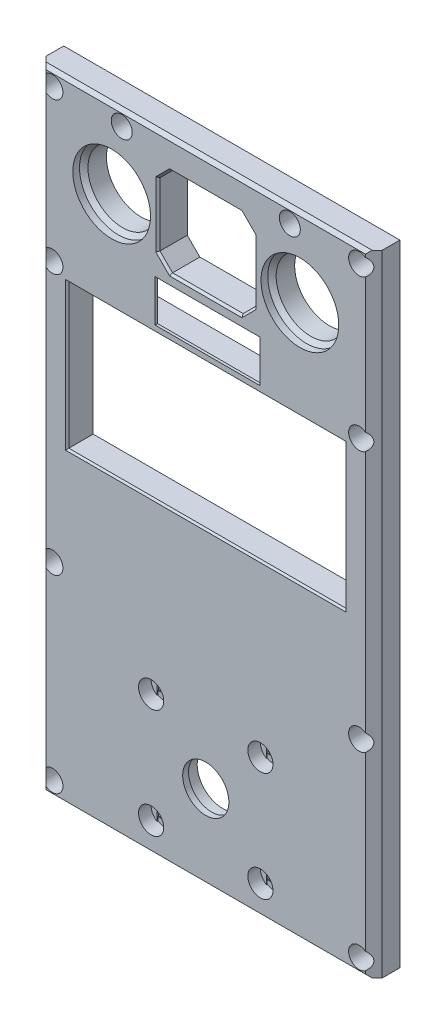
SolidWorks part; units mm, degrees
ref_plane "Front Plane" through (0, 0, 0) normal (0, 0, 1) x (1, 0, 0)
ref_plane "Top Plane" through (0, 0, 0) normal (0, 1, 0) x (1, 0, 0)
ref_plane "Right Plane" through (0, 0, 0) normal (1, 0, 0) x (0, 0, -1)
sketch "Sketch1" plane through (0, 0, 0) normal (0, 0, 1) x (1, 0, 0)
  line L1 (-40, -75) -> (40, -75)
  line L2 (-40, -75) -> (-40, 75)
  line L3 (-40, 75) -> (40, 75)
  line L4 (40, -75) -> (40, 75)
  line L5 (-40, -75) -> (40, 75) construction
  line L6 (-40, 75) -> (40, -75) construction
  line L7 (-33, -68) -> (33, -68)
  line L8 (-33, -68) -> (-33, 68)
  line L9 (-33, 68) -> (33, 68)
  line L10 (33, -68) -> (33, 68)
  line L11 (-33, -68) -> (33, 68) construction
  line L12 (-33, 68) -> (33, -68) construction
  point P0 (0, 0)
  point P6 (0, 0)
  dimension "D1" = 150
  dimension "D2" = 80
  dimension "D3" = 7
  dimension "D4" = 7
extrude "Boss-Extrude1" add sketch "Sketch1" along normal blind 7
sketch "Sketch2" plane through (0, 0, 7) normal (0, 0, 1) x (1, 0, 0)
  line L0 (33, -68) -> (33, 68) construction
  line L1 (-33, -68) -> (33, -68)
  line L2 (-33, -68) -> (-33, -32)
  line L3 (-33, -32) -> (33, -32)
  line L4 (33, -68) -> (33, -32)
  dimension "D1" = 36
extrude "Boss-Extrude2" add sketch "Sketch2" against normal up to surface (7 mm away) up to face at (0, 0, 0)
sketch "Sketch3" plane through (0, 0, 0) normal (0, 0, -1) x (-1, 0, 0)
  line L0 (0, -75) -> (0, -55) construction
  line L1 (40, -75) -> (-40, -75) construction
  circle A0 centre (0, -55) radius 5.5
  dimension "D1" = 11
  dimension "D2" = 20
extrude "Cut-Extrude1" cut sketch "Sketch3" against normal through all
sketch "Sketch4" plane through (0, 0, 0) normal (0, 0, -1) x (-1, 0, 0)
  circle A0 centre (0, -55) radius 6.05
  dimension "D1" = 12.1
extrude "Cut-Extrude2" cut sketch "Sketch4" against normal offset from surface (5.6 mm away) 1.4 up to face at (-5.5, -55, 7)
sketch "Sketch5" plane through (0, 0, 0) normal (0, 0, -1) x (-1, 0, 0)
  circle A0 centre (0, -55) radius 11.1
  dimension "D1" = 22.2
extrude "Cut-Extrude3" cut sketch "Sketch5" against normal offset from surface (3 mm away) 2.6 up to face at (-6.05, -55, 5.6)
sketch "Sketch6" plane through (0, 0, 0) normal (0, 0, -1) x (-1, 0, 0)
  line L1 (-13, -68) -> (13, -68) construction
  line L2 (-13, -68) -> (-13, -42) construction
  line L3 (-13, -42) -> (13, -42) construction
  line L4 (13, -68) -> (13, -42) construction
  line L5 (-13, -68) -> (13, -42) construction
  line L6 (-13, -42) -> (13, -68) construction
  circle A0 centre (-13, -42) radius 1.6
  circle A1 centre (13, -42) radius 1.6
  circle A2 centre (13, -68) radius 1.6
  circle A3 centre (-13, -68) radius 1.6
  point P0 (0, -55)
  dimension "D2" = 3.2
  dimension "D1" = 26
extrude "Cut-Extrude4" cut sketch "Sketch6" against normal through all
sketch "Sketch7" plane through (0, 0, 0) normal (0, 0, -1) x (-1, 0, 0)
  line L1 (-25, -74) -> (25, -74)
  line L2 (-25, -74) -> (-25, -36)
  line L3 (-25, -36) -> (25, -36)
  line L4 (25, -74) -> (25, -36)
  line L5 (-25, -74) -> (25, -36) construction
  line L6 (-25, -36) -> (25, -74) construction
  point P0 (0, -55)
  dimension "D1" = 50
  dimension "D2" = 38
extrude "Cut-Extrude5" cut sketch "Sketch7" against normal blind 1
sketch "Sketch8" plane through (0, 0, 7) normal (0, 0, 1) x (1, 0, 0)
  circle A0 centre (-13, -42) radius 3
  circle A1 centre (13, -42) radius 3
  circle A2 centre (13, -68) radius 3
  circle A3 centre (-13, -68) radius 3
  dimension "D1" = 6
extrude "Cut-Extrude6" cut sketch "Sketch8" against normal blind 3
sketch "Sketch9" plane through (0, 0, 7) normal (0, 0, 1) x (1, 0, 0)
  line L0 (-40, 75) -> (-40, -75) construction
  line L1 (-36.5, -71.5) -> (36.5, -71.5) construction
  line L2 (-36.5, -71.5) -> (-36.5, 71.5) construction
  line L3 (-36.5, 71.5) -> (36.5, 71.5) construction
  line L4 (36.5, -71.5) -> (36.5, 71.5) construction
  line L5 (-36.5, -71.5) -> (36.5, 71.5) construction
  line L6 (-36.5, 71.5) -> (36.5, -71.5) construction
  line L7 (40, 75) -> (-40, 75) construction
  circle A0 centre (-36.5, 71.5) radius 1.35
  circle A1 centre (36.5, 71.5) radius 1.35
  circle A2 centre (36.5, -71.5) radius 1.35
  circle A3 centre (-36.5, -71.5) radius 1.35
  circle A6 centre (-36.5, 35.5) radius 1.35
  circle A7 centre (-36.5, -26.5) radius 1.35
  circle A8 centre (36.5, -26.5) radius 1.35
  circle A9 centre (36.5, 35.5) radius 1.35
  point P0 (0, 0)
  dimension "D3" = 2.7
  dimension "D4" = 45
  dimension "D5" = 36
  dimension "D1" = 3.5
  dimension "D2" = 3.5
extrude "Cut-Extrude7" cut sketch "Sketch9" against normal through all
sketch "Sketch10" plane through (0, 0, 7) normal (0, 0, 1) x (1, 0, 0)
  circle A0 centre (-36.5, 71.5) radius 2.5
  circle A1 centre (36.5, 71.5) radius 2.5
  circle A2 centre (-36.5, 35.5) radius 2.5
  circle A3 centre (-36.5, -26.5) radius 2.5
  circle A4 centre (-36.5, -71.5) radius 2.5
  circle A5 centre (36.5, -71.5) radius 2.5
  circle A6 centre (36.5, 35.5) radius 2.5
  circle A7 centre (36.5, -26.5) radius 2.5
  dimension "D1" = 5
extrude "Cut-Extrude8" cut sketch "Sketch10" against normal blind 5
chamfer "Chamfer1" distance 2 angle 45 2 edges at (-40, 0, 7) (40, 0, 7)
sketch "Sketch11" plane through (0, 0, 7) normal (0, 0, 1) x (1, 0, 0)
  line L0 (33, -32) -> (33, 68) construction
  line L1 (-33, -32) -> (33, -32)
  line L2 (-33, -32) -> (-33, -1.5)
  line L3 (-33, -1.5) -> (33, -1.5)
  line L4 (33, -32) -> (33, -1.5)
  line L5 (-38, -75) -> (38, -75) construction
  dimension "D1" = 73.5
extrude "Boss-Extrude3" add sketch "Sketch11" against normal up to surface (7 mm away) up to face at (37.85, 71.5, 0)
sketch "Sketch12" plane through (0, 0, 2) normal (0, 0, 1) x (1, 0, 0)
  line L2 (-37.85, -73.6042) -> (-37.85, -69.3958)
  line L4 (-35.15, -73.6042) -> (-35.15, -69.3958)
  line L5 (-37.85, -73.6042) -> (-35.15, -69.3958) construction
  line L6 (-37.85, -69.3958) -> (-35.15, -73.6042) construction
  line L8 (-37.85, -28.6042) -> (-37.85, -24.3958)
  line L10 (-35.15, -28.6042) -> (-35.15, -24.3958)
  line L11 (-37.85, -28.6042) -> (-35.15, -24.3958) construction
  line L12 (-37.85, -24.3958) -> (-35.15, -28.6042) construction
  line L14 (-37.85, 33.3958) -> (-37.85, 37.6042)
  line L16 (-35.15, 33.3958) -> (-35.15, 37.6042)
  line L17 (-37.85, 33.3958) -> (-35.15, 37.6042) construction
  line L18 (-37.85, 37.6042) -> (-35.15, 33.3958) construction
  line L20 (-37.85, 69.3958) -> (-37.85, 73.6042)
  line L22 (-35.15, 69.3958) -> (-35.15, 73.6042)
  line L23 (-37.85, 69.3958) -> (-35.15, 73.6042) construction
  line L24 (-37.85, 73.6042) -> (-35.15, 69.3958) construction
  arc A0 (-38, -73.5) -> (-38, -69.5) centre (-36.5, -71.5) ccw construction
  circle A1 centre (-36.5, -26.5) radius 2.5 construction
  circle A2 centre (-36.5, 35.5) radius 2.5 construction
  arc A3 (-38, 69.5) -> (-38, 73.5) centre (-36.5, 71.5) ccw construction
  circle A4 centre (-36.5, 71.5) radius 1.35 construction
  circle A5 centre (-36.5, 71.5) radius 2.5 construction
  arc A6 (-35.15, 73.6042) -> (-37.85, 73.6042) centre (-36.5, 71.5) ccw
  arc A7 (-37.85, 69.3958) -> (-35.15, 69.3958) centre (-36.5, 71.5) ccw
  circle A8 centre (-36.5, 35.5) radius 1.35 construction
  arc A9 (-37.85, 33.3958) -> (-35.15, 33.3958) centre (-36.5, 35.5) ccw
  arc A10 (-35.15, 37.6042) -> (-37.85, 37.6042) centre (-36.5, 35.5) ccw
  circle A11 centre (-36.5, -26.5) radius 1.35 construction
  arc A12 (-37.85, -28.6042) -> (-35.15, -28.6042) centre (-36.5, -26.5) ccw
  arc A13 (-35.15, -24.3958) -> (-37.85, -24.3958) centre (-36.5, -26.5) ccw
  circle A14 centre (-36.5, -71.5) radius 1.35 construction
  arc A16 (-37.85, -73.6042) -> (-35.15, -73.6042) centre (-36.5, -71.5) ccw
  arc A18 (-35.15, -69.3958) -> (-37.85, -69.3958) centre (-36.5, -71.5) ccw
  point P0 (-36.5, -71.5)
  point P9 (-36.5, -26.5)
  point P17 (-36.5, 35.5)
  point P25 (-36.5, 71.5)
extrude "Cut-Extrude9" cut sketch "Sketch12" against normal blind 0.2
sketch "Sketch13" plane through (0, 0, 1.8) normal (0, 0, 1) x (1, 0, 0)
  line L0 (-35.15, -71.5) -> (-35.15, -69.3958) construction
  line L1 (-37.85, -72.85) -> (-35.15, -72.85)
  line L2 (-37.85, -72.85) -> (-37.85, -70.15)
  line L3 (-37.85, -70.15) -> (-35.15, -70.15)
  line L4 (-35.15, -72.85) -> (-35.15, -70.15)
  line L5 (-37.85, -72.85) -> (-35.15, -70.15) construction
  line L6 (-37.85, -70.15) -> (-35.15, -72.85) construction
  line L7 (-35.15, -26.5) -> (-35.15, -24.3958) construction
  line L8 (-37.85, -27.85) -> (-35.15, -27.85)
  line L9 (-37.85, -27.85) -> (-37.85, -25.15)
  line L10 (-37.85, -25.15) -> (-35.15, -25.15)
  line L11 (-35.15, -27.85) -> (-35.15, -25.15)
  line L12 (-37.85, -27.85) -> (-35.15, -25.15) construction
  line L13 (-37.85, -25.15) -> (-35.15, -27.85) construction
  line L14 (-35.15, 33.3958) -> (-35.15, 37.6042) construction
  line L15 (-37.85, 34.15) -> (-35.15, 34.15)
  line L16 (-37.85, 34.15) -> (-37.85, 36.85)
  line L17 (-37.85, 36.85) -> (-35.15, 36.85)
  line L18 (-35.15, 34.15) -> (-35.15, 36.85)
  line L19 (-37.85, 34.15) -> (-35.15, 36.85) construction
  line L20 (-37.85, 36.85) -> (-35.15, 34.15) construction
  line L21 (-35.15, 69.3958) -> (-35.15, 73.6042) construction
  line L22 (-37.85, 70.15) -> (-35.15, 70.15)
  line L23 (-37.85, 70.15) -> (-37.85, 72.85)
  line L24 (-37.85, 72.85) -> (-35.15, 72.85)
  line L25 (-35.15, 70.15) -> (-35.15, 72.85)
  line L26 (-37.85, 70.15) -> (-35.15, 72.85) construction
  line L27 (-37.85, 72.85) -> (-35.15, 70.15) construction
  arc A0 (-35.15, -71.5) -> (-37.85, -71.5) centre (-36.5, -71.5) ccw construction
  arc A1 (-35.15, -26.5) -> (-37.85, -26.5) centre (-36.5, -26.5) ccw construction
  arc A2 (-35.15, 35.5) -> (-37.85, 35.5) centre (-36.5, 35.5) ccw construction
  arc A3 (-35.15, 71.5) -> (-37.85, 71.5) centre (-36.5, 71.5) ccw construction
  point P0 (-36.5, -71.5)
  point P11 (-36.5, -26.5)
  point P22 (-36.5, 35.5)
  point P33 (-36.5, 71.5)
extrude "Cut-Extrude10" cut sketch "Sketch13" against normal blind 0.2
sketch "Sketch14" plane through (0, 0, 4) normal (0, 0, 1) x (1, 0, 0)
  line L2 (-14.6, -44.5377) -> (-14.6, -39.4623)
  line L4 (-11.4, -44.5377) -> (-11.4, -39.4623)
  line L5 (-14.6, -44.5377) -> (-11.4, -39.4623) construction
  line L6 (-14.6, -39.4623) -> (-11.4, -44.5377) construction
  line L8 (-14.6, -70.5377) -> (-14.6, -65.4623)
  line L10 (-11.4, -70.5377) -> (-11.4, -65.4623)
  line L11 (-14.6, -70.5377) -> (-11.4, -65.4623) construction
  line L12 (-14.6, -65.4623) -> (-11.4, -70.5377) construction
  circle A0 centre (-13, -42) radius 3 construction
  circle A1 centre (-13, -68) radius 3 construction
  circle A2 centre (-13, -42) radius 3 construction
  arc A3 (-14.6, -44.5377) -> (-11.4, -44.5377) centre (-13, -42) ccw
  arc A4 (-14.6, -70.5377) -> (-11.4, -70.5377) centre (-13, -68) ccw
  circle A5 centre (-13, -42) radius 1.6 construction
  circle A6 centre (-13, -68) radius 1.6 construction
  arc A7 (-11.4, -39.4623) -> (-14.6, -39.4623) centre (-13, -42) ccw
  arc A8 (-11.4, -65.4623) -> (-14.6, -65.4623) centre (-13, -68) ccw
  point P0 (-13, -42)
  point P8 (-13, -68)
extrude "Cut-Extrude11" cut sketch "Sketch14" against normal blind 0.2
sketch "Sketch15" plane through (0, 0, 3.8) normal (0, 0, 1) x (1, 0, 0)
  line L0 (-11.4, -42) -> (-11.4, -39.4623) construction
  line L1 (-14.6, -43.6) -> (-11.4, -43.6)
  line L2 (-14.6, -43.6) -> (-14.6, -40.4)
  line L3 (-14.6, -40.4) -> (-11.4, -40.4)
  line L4 (-11.4, -43.6) -> (-11.4, -40.4)
  line L5 (-14.6, -43.6) -> (-11.4, -40.4) construction
  line L6 (-14.6, -40.4) -> (-11.4, -43.6) construction
  line L7 (-11.4, -68) -> (-11.4, -65.4623) construction
  line L8 (-14.6, -69.6) -> (-11.4, -69.6)
  line L9 (-14.6, -69.6) -> (-14.6, -66.4)
  line L10 (-14.6, -66.4) -> (-11.4, -66.4)
  line L11 (-11.4, -69.6) -> (-11.4, -66.4)
  line L12 (-14.6, -69.6) -> (-11.4, -66.4) construction
  line L13 (-14.6, -66.4) -> (-11.4, -69.6) construction
  arc A0 (-11.4, -68) -> (-14.6, -68) centre (-13, -68) ccw construction
  arc A1 (-14.6, -42) -> (-11.4, -42) centre (-13, -42) ccw construction
  point P0 (-13, -42)
  point P8 (-13, -68)
extrude "Cut-Extrude12" cut sketch "Sketch15" against normal blind 0.2
mirror "Mirror1" about plane through (0, 0, 0) normal (1, 0, 0) of "Cut-Extrude10", "Cut-Extrude11", "Cut-Extrude12", "Cut-Extrude9"
chamfer "Chamfer2" distance 0.4 angle 45 4 edges at (33, 33.25, 7) (0, 68, 7) (0, -1.5, 7) (-33, 33.25, 7)
chamfer "Chamfer3" distance 0.8 angle 45 4 edges at (-40, 0, 0) (40, 0, 0) (0, -75, 7) (0, 75, 7)
sketch "Sketch16" plane through (0, 0, 0) normal (1, 0, 0) x (0, 0, -1)
  line L0 (0, -4) -> (0, -15.4)
  line L1 (0, 75) -> (0, -75) construction
  line L2 (0, -15.4) -> (3.2, -12.2)
  line L3 (3.2, -12.2) -> (3.2, -7.2)
  line L4 (3.2, -7.2) -> (0, -4)
  line L5 (0, -15.4) -> (0, -19.4) construction
  line L6 (0.6, -7.7) -> (2.6, -7.7)
  line L7 (0.6, -7.7) -> (0.6, -11.7)
  line L8 (0.6, -11.7) -> (2.6, -11.7)
  line L9 (2.6, -7.7) -> (2.6, -11.7)
  line L10 (-1.046, -17.4) -> (12.8392, -17.4) construction
  line L11 (2.6, -27.1) -> (2.6, -23.1)
  line L12 (0.6, -23.1) -> (2.6, -23.1)
  line L13 (0.6, -27.1) -> (0.6, -23.1)
  line L14 (0.6, -27.1) -> (2.6, -27.1)
  line L15 (3.2, -27.6) -> (0, -30.8)
  line L16 (3.2, -22.6) -> (3.2, -27.6)
  line L17 (0, -19.4) -> (3.2, -22.6)
  line L18 (0, -30.8) -> (0, -19.4)
  point P10 (2.6, -9.7)
  point P11 (3.2, -9.7)
  point P24 (0, -17.4)
  dimension "D1" = 5
  dimension "D2" = 2
  dimension "D3" = 0.6
  dimension "D4" = 0.6
  dimension "D5" = 45
  dimension "D6" = 4
  dimension "D7" = 4
  dimension "D8" = 4
extrude "Boss-Extrude4" add sketch "Sketch16" along normal mid plane 2
pattern_linear "LPattern1" count 2 spacing 20 along (1, 0, 0) count 2 spacing 20 along (-1, 0, 0) of "Boss-Extrude4"
sketch "Sketch17" plane through (0, 0, 0) normal (0, 0, -1) x (-1, 0, 0)
  line L0 (-20, 71.5) -> (20, 71.5) construction
  line L1 (-39.2, 75) -> (39.2, 75) construction
  circle A0 centre (-36.5, 71.5) radius 1.35 construction
  circle A1 centre (-36.5, 71.5) radius 1.35 construction
  circle A2 centre (-20, 71.5) radius 1.35
  circle A3 centre (20, 71.5) radius 1.35
  point P3 (0, 71.5)
  point P6 (0, 75)
  dimension "D1" = 40
extrude "Cut-Extrude13" cut sketch "Sketch17" against normal through all
sketch "Sketch18" plane through (0, 0, 7) normal (0, 0, 1) x (1, 0, 0)
  circle A0 centre (-20, 71.5) radius 2.5
  circle A1 centre (20, 71.5) radius 2.5
  arc A2 (-38, 69.5) -> (-38, 73.5) centre (-36.5, 71.5) ccw construction
extrude "Cut-Extrude14" cut sketch "Sketch18" against normal up to surface (5 mm away) up to face at (38.425, 71.5, 2)
sketch "Sketch19" plane through (0, 0, 2) normal (0, 0, 1) x (1, 0, 0)
  line L2 (-21.35, 69.3958) -> (-21.35, 73.6042)
  line L4 (-18.65, 69.3958) -> (-18.65, 73.6042)
  line L5 (-21.35, 69.3958) -> (-18.65, 73.6042) construction
  line L6 (-21.35, 73.6042) -> (-18.65, 69.3958) construction
  line L8 (18.65, 69.3958) -> (18.65, 73.6042)
  line L10 (21.35, 69.3958) -> (21.35, 73.6042)
  line L11 (18.65, 69.3958) -> (21.35, 73.6042) construction
  line L12 (18.65, 73.6042) -> (21.35, 69.3958) construction
  circle A0 centre (-20, 71.5) radius 2.5 construction
  circle A1 centre (20, 71.5) radius 2.5 construction
  circle A2 centre (20, 71.5) radius 1.35 construction
  circle A3 centre (-20, 71.5) radius 1.35 construction
  circle A4 centre (-20, 71.5) radius 2.5 construction
  arc A5 (18.65, 69.3958) -> (21.35, 69.3958) centre (20, 71.5) ccw
  arc A6 (-18.65, 73.6042) -> (-21.35, 73.6042) centre (-20, 71.5) ccw
  arc A7 (21.35, 73.6042) -> (18.65, 73.6042) centre (20, 71.5) ccw
  arc A8 (-21.35, 69.3958) -> (-18.65, 69.3958) centre (-20, 71.5) ccw
  point P0 (-20, 71.5)
  point P8 (20, 71.5)
extrude "Cut-Extrude15" cut sketch "Sketch19" against normal blind 0.2
sketch "Sketch20" plane through (0, 0, 1.8) normal (0, 0, 1) x (1, 0, 0)
  line L0 (-18.65, 69.3958) -> (-18.65, 73.6042) construction
  line L1 (-21.35, 70.15) -> (-18.65, 70.15)
  line L2 (-21.35, 70.15) -> (-21.35, 72.85)
  line L3 (-21.35, 72.85) -> (-18.65, 72.85)
  line L4 (-18.65, 70.15) -> (-18.65, 72.85)
  line L5 (-21.35, 70.15) -> (-18.65, 72.85) construction
  line L6 (-21.35, 72.85) -> (-18.65, 70.15) construction
  line L7 (21.35, 71.5) -> (21.35, 73.6042) construction
  line L8 (18.65, 70.15) -> (21.35, 70.15)
  line L9 (18.65, 70.15) -> (18.65, 72.85)
  line L10 (18.65, 72.85) -> (21.35, 72.85)
  line L11 (21.35, 70.15) -> (21.35, 72.85)
  line L12 (18.65, 70.15) -> (21.35, 72.85) construction
  line L13 (18.65, 72.85) -> (21.35, 70.15) construction
  arc A0 (18.65, 71.5) -> (21.35, 71.5) centre (20, 71.5) ccw construction
  point P0 (-20, 71.5)
  point P8 (20, 71.5)
extrude "Cut-Extrude16" cut sketch "Sketch20" against normal blind 0.2
sketch "Skizze4" plane through (0, 0, 0) normal (0, 0, -1) x (-1, 0, 0)
  line L1 (21, -4) -> (-21, -4)
  line L2 (21, -4) -> (21, -30.8)
  line L3 (21, -30.8) -> (-21, -30.8)
  line L4 (-21, -4) -> (-21, -30.8)
extrude "Schnitt-Linear austragen1" cut sketch "Skizze4" along normal up to surface (3.2 mm away) up to face at (-20, -9.7, -3.2)
sketch "Skizze6" plane through (0, 0, 7) normal (0, 0, 1) x (1, 0, 0)
  line L0 (11.4, 68.4) -> (33.4, 46.4) construction
  line L1 (33.4, 68.4) -> (11.4, 68.4)
  line L2 (33.4, 68.4) -> (33.4, 46.4)
  line L3 (33.4, 46.4) -> (11.4, 46.4)
  line L4 (11.4, 68.4) -> (11.4, 46.4)
  line L5 (22.4, 68.4) -> (22.4, 46.4) construction
  circle A0 centre (22.4, 56.4) radius 8.25
  point P10 (22.4, 57.4)
  dimension "D1" = 16.5
  dimension "D2" = 22
  dimension "D3" = 22
  dimension "D4" = 1
extrude "Aufsatz-Linear austragen1" add sketch "Skizze6" against normal up to surface (7 mm away) up to face at (18.65, 71.5, 0)
sketch "Skizze7" plane through (0, 0, 7) normal (0, 0, 1) x (1, 0, 0)
  circle A0 centre (22.4, 56.4) radius 9.25
  dimension "D1" = 18.5
extrude "Schnitt-Linear austragen2" cut sketch "Skizze7" against normal blind 1.6
chamfer "Fase6" distance 0.5 angle 45 2 edges at (11.4, 57.4, 7) (22.4, 46.4, 7)
chamfer "Fase7" distance 4 angle 45 1 edges at (11.4, 46.4, 3.25)
chamfer "Fase8" distance 1 angle 45 1 edges at (30.65, 56.4, 5.4)
mirror "Mirror2" about plane through (0, 0, 0) normal (1, 0, 0) of "Fase6", "Schnitt-Linear austragen2", "Fase8", "Aufsatz-Linear austragen1", "Fase7"
sketch "Sketch21" plane through (0, 0, 7) normal (0, 0, 1) x (1, 0, 0)
  line L0 (33.4, 46.9) -> (33.4, -1.9) construction
  line L1 (-33.4, 46.9) -> (-14.9, 46.9)
  line L2 (-33.4, 46.9) -> (-33.4, 32.9)
  line L3 (-33.4, 32.9) -> (33.4, 32.9)
  line L4 (33.4, 46.9) -> (33.4, 32.9)
  line L5 (-14.9, 46.9) -> (-11.4, 50.4)
  line L6 (-11.4, 50.4) -> (-11.4, 46.9)
  line L7 (11.4, 50.4) -> (14.9, 46.9)
  line L8 (11.4, 50.4) -> (11.4, 46.9)
  line L9 (-11.4, 46.9) -> (11.4, 46.9)
  line L10 (14.9, 46.9) -> (33.4, 46.9)
  dimension "D1" = 14
extrude "Boss-Extrude5" add sketch "Sketch21" against normal up to surface (7 mm away) up to face at (0, 41.94, 0)
chamfer "Chamfer4" distance 0.5 angle 45 3 edges at (11.4, 48.65, 7) (-11.4, 48.65, 7) (0, 46.9, 7)
sketch "Sketch22" plane through (0, 0, 0) normal (0, 0, -1) x (-1, 0, 0)
  line L0 (0, 46.9) -> (0, 32.9) construction
  line L1 (-11.4, 46.9) -> (11.4, 46.9) construction
  line L2 (33, 32.9) -> (-33, 32.9) construction
  line L4 (-18.95, 33.75) -> (18.95, 33.75)
  line L5 (-18.95, 33.75) -> (-18.95, 46.05)
  line L6 (-18.95, 46.05) -> (18.95, 46.05)
  line L7 (18.95, 33.75) -> (18.95, 46.05)
  line L8 (-18.95, 33.75) -> (18.95, 46.05) construction
  line L9 (-18.95, 46.05) -> (18.95, 33.75) construction
  point P6 (0, 39.9)
  dimension "D1" = 37.9
  dimension "D2" = 12.3
extrude "Cut-Extrude17" cut sketch "Sketch22" against normal offset from surface (6.4 mm away) 0.6 up to face at (0, 15.5, 7)
sketch "Sketch23" plane through (0, 0, 6.4) normal (0, 0, -1) x (-1, 0, 0)
  line L0 (-18.95, 46.05) -> (-18.95, 33.75) construction
  line L1 (-12.95, 34.55) -> (12.05, 34.55)
  line L2 (-12.95, 34.55) -> (-12.95, 44.55)
  line L3 (-12.95, 44.55) -> (12.05, 44.55)
  line L4 (12.05, 34.55) -> (12.05, 44.55)
  line L5 (-12.95, 34.55) -> (12.05, 44.55) construction
  line L6 (-12.95, 44.55) -> (12.05, 34.55) construction
  line L7 (-18.95, 46.05) -> (18.95, 46.05) construction
  point P0 (-0.45, 39.55)
  dimension "D1" = 25
  dimension "D2" = 10
  dimension "D3" = 6
  dimension "D4" = 1.5
extrude "Cut-Extrude18" cut sketch "Sketch23" against normal through all
chamfer "Chamfer5" distance 0.4 angle 45 1 edges at (0, 32.9, 7)
sketch "Sketch24" plane through (0, 0, 7) normal (0, 0, 1) x (1, 0, 0)
  line L1 (-11.9, 68.4) -> (11.9, 68.4)
  line L2 (-11.9, 68.4) -> (-11.9, 46.4)
  line L3 (-11.9, 46.4) -> (11.9, 46.4)
  line L4 (11.9, 68.4) -> (11.9, 46.4)
  line L5 (-11.4, 68) -> (11.4, 68)
  line L6 (-11.4, 68) -> (-11.4, 46.9)
  line L7 (-11.4, 46.9) -> (11.4, 46.9)
  line L8 (11.4, 68) -> (11.4, 46.9)
extrude "Boss-Extrude6" add sketch "Sketch24" against normal up to vertex (0.5 mm away) up to point (11.4, 46.9, 6.5)
chamfer "Chamfer7" distance 3 angle 45 4 edges at (11.4, 46.9, 3.5) (11.4, 68, 3.5) (-11.4, 68, 3.5) (-11.4, 46.9, 3.5)
chamfer "Chamfer8" distance 0.5 angle 45 8 edges at (-9.9, 48.4, 7) (0, 46.9, 7) (9.9, 48.4, 7) (11.4, 57.45, 7) (9.9, 66.5, 7) (0, 68, 7) (-9.9, 66.5, 7) (-11.4, 57.45, 7)
chamfer "Chamfer9" distance 0.8 angle 45 6 edges at (-33, 15.7, 0) (0, 32.9, 0) (33, 15.7, 0) (0, -1.5, 0) (0, -75, 0) (0, 75, 0)
